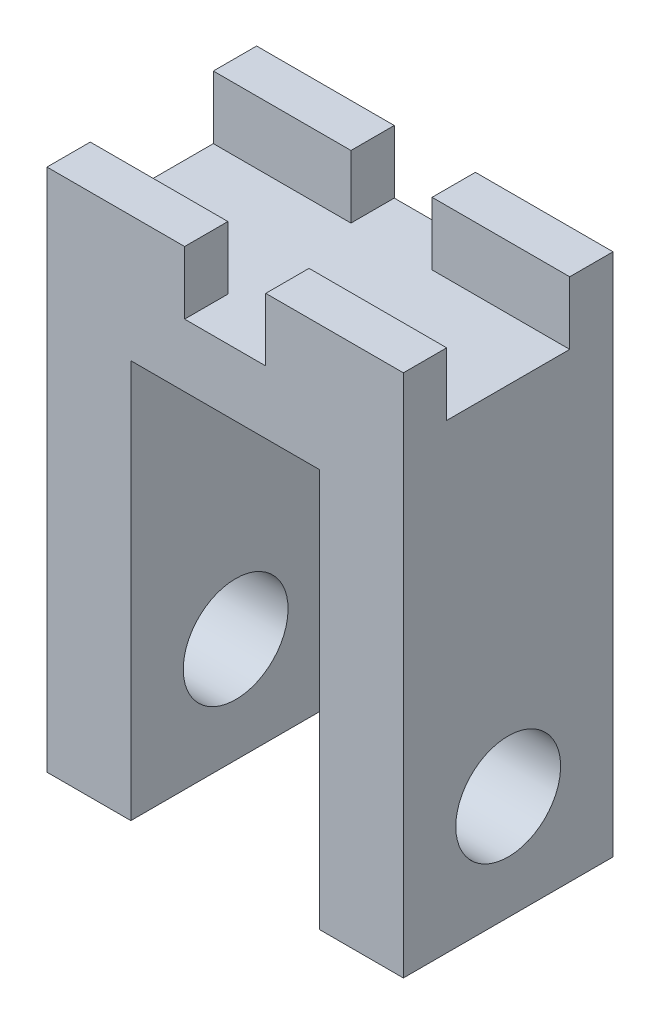
SolidWorks part; units mm, degrees
ref_plane "Front Plane" through (0, 0, 0) normal (0, 0, 1) x (1, 0, 0)
ref_plane "Top Plane" through (0, 0, 0) normal (0, 1, 0) x (1, 0, 0)
ref_plane "Right Plane" through (0, 0, 0) normal (1, 0, 0) x (0, 0, -1)
sketch "Sketch1" plane through (0, 0, 0) normal (0, 0, 1) x (1, 0, 0)
  line L1 (-4.5, 9.5) -> (4.5, 9.5)
  line L2 (-4.5, 9.5) -> (-4.5, -9.5)
  line L3 (-4.5, -9.5) -> (4.5, -9.5)
  line L4 (4.5, 9.5) -> (4.5, -9.5)
  line L5 (-4.5, 9.5) -> (4.5, -9.5) construction
  line L6 (-4.5, -9.5) -> (4.5, 9.5) construction
  line L7 (-8.5, 12.5) -> (8.5, 12.5)
  line L8 (-8.5, 12.5) -> (-8.5, -9.5)
  line L9 (-8.5, -9.5) -> (8.5, -9.5)
  line L10 (8.5, 12.5) -> (8.5, -9.5)
  point P0 (0, 0)
  point P10 (0, 12.5)
  point P11 (0, 9.5)
  dimension "D1" = 4
  dimension "D2" = 9
  dimension "D3" = 19
  dimension "D4" = 3
extrude "Boss-Extrude1" add sketch "Sketch1" along normal blind 10 contours L10 L7 L8 L9 L2 L1 L4 region at (-4.778, 0, 0)
sketch "Sketch2" plane through (-8.5, 0, 0) normal (-1, 0, 0) x (0, 0, 1)
  line L0 (10, 9.5) -> (0, 9.5) construction
  line L1 (10, 9.5) -> (0, 9.5)
  line L2 (10, -9.5) -> (0, -9.5) construction
  circle A0 centre (5, -4.5) radius 20 construction
  circle A1 centre (5, -4.5) radius 2.5
  point P2 (10.4934, -11.5323)
  point P5 (10, -7.3034)
  point P6 (5, 9.5)
  dimension "D1" = 40
  dimension "D2" = 5
  dimension "D3" = 5
extrude "Cut-Extrude1" cut sketch "Sketch2" against normal through all both and the other way through all contours A1 region at (-8.5, -4.5, 5)
sketch "Sketch4" plane through (0, 12.5, 0) normal (0, 1, 0) x (1, 0, 0)
  line L1 (-8.5, 0) -> (-1.935, 0)
  line L2 (-8.5, 0) -> (-8.5, -2.065)
  line L3 (-8.5, -2.065) -> (-1.935, -2.065)
  line L4 (-1.935, 0) -> (-1.935, -2.065)
  line L5 (-8.5, -10) -> (-1.935, -10)
  line L6 (-8.5, -10) -> (-8.5, -7.935)
  line L7 (-8.5, -7.935) -> (-1.935, -7.935)
  line L8 (-1.935, -10) -> (-1.935, -7.935)
  line L9 (8.5, 0) -> (1.935, 0)
  line L10 (8.5, 0) -> (8.5, -2.065)
  line L11 (8.5, -2.065) -> (1.935, -2.065)
  line L12 (1.935, 0) -> (1.935, -2.065)
  line L13 (8.5, -10) -> (1.935, -10)
  line L14 (8.5, -10) -> (8.5, -7.935)
  line L15 (8.5, -7.935) -> (1.935, -7.935)
  line L16 (1.935, -10) -> (1.935, -7.935)
  point P19 (-1.3066, -4.1694)
  dimension "D1" = 5.87
  dimension "D2" = 3.87
extrude "Boss-Extrude2" add sketch "Sketch4" along normal blind 3 contours L10 L9 L12 L11 | L2 L1 L4 L3 | L6 L5 L8 L7 | L14 L13 L16 L15
